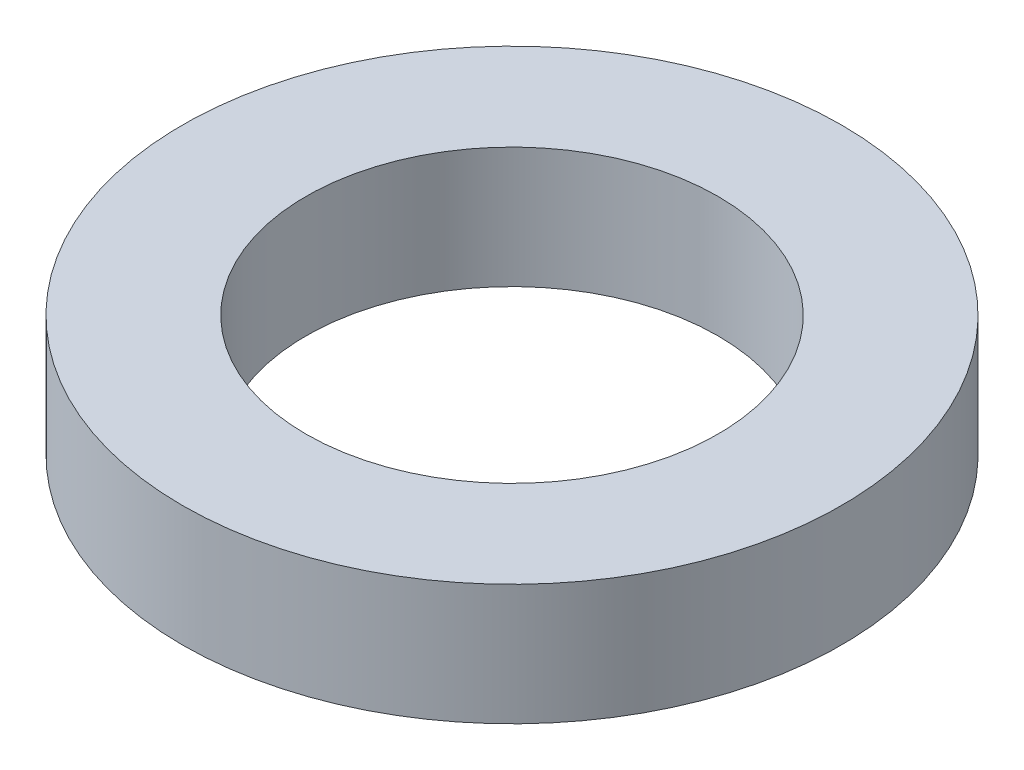
SolidWorks part; units mm, degrees
ref_plane "Front Plane" through (0, 0, 0) normal (0, 0, 1) x (1, 0, 0)
ref_plane "Top Plane" through (0, 0, 0) normal (0, 1, 0) x (1, 0, 0)
ref_plane "Right Plane" through (0, 0, 0) normal (1, 0, 0) x (0, 0, -1)
sketch "Sketch1" plane through (0, 0, 0) normal (0, 1, 0) x (1, 0, 0)
  circle A0 centre (0, 0) radius 60
  dimension "FLANGE_OD" = 120
extrude "Boss-Extrude1" add sketch "Sketch1" along normal blind 22
sketch "Sketch2" plane through (0, 0, 0) normal (0, 1, 0) x (1, 0, 0)
  circle A0 centre (0, 0) radius 37.5
  dimension "BORE_D" = 75
extrude "Cut-Extrude1" cut sketch "Sketch2" along normal through all
sketch "Sketch3" plane through (0, 22, 0) normal (0, 1, 0) x (1, 0, 0)
  circle A0 centre (0, 0) radius 24.5221 construction
  circle A1 centre (-24.5221, 0) radius 3.1877
  dimension "BOLT_D" = 6.3753
  dimension "BOLT_PCD" = 49.0442
extrude "Cut-Extrude2" cut sketch "Sketch3" against normal blind 17.3534 rebuild error yes
pattern_circular "CirPattern1" count 8 over 360 rebuild error yes
